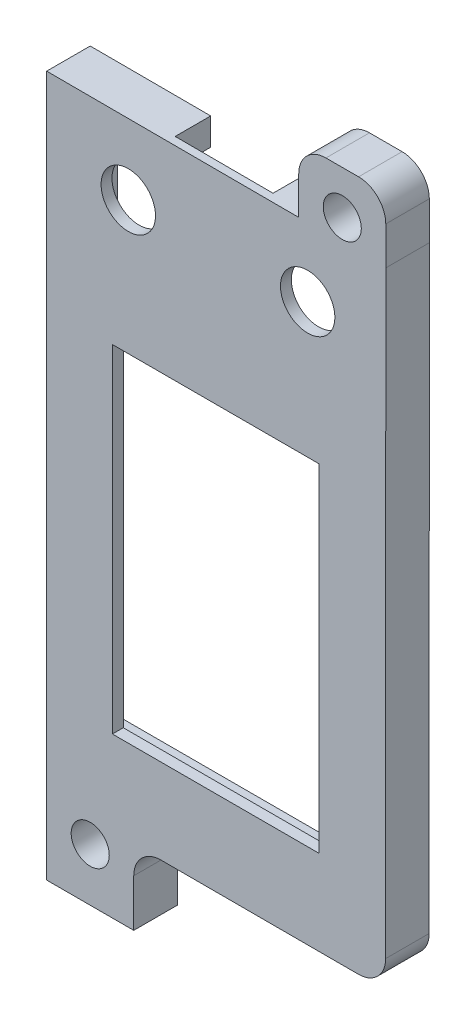
SolidWorks part; units mm, degrees
ref_plane "Front" through (0, 0, 0) normal (0, 0, 1) x (1, 0, 0)
ref_plane "Top" through (0, 0, 0) normal (0, 1, 0) x (1, 0, 0)
ref_plane "Side" through (0, 0, 0) normal (1, 0, 0) x (0, 0, -1)
ref_axis "X_Axis" through (-20.1896, 0, 0) along (1, 0, 0)
ref_axis "Y_Axis" through (0, -14.8261, 0) along (0, 1, 0)
ref_axis "Z_Axis" through (0, 0, -19.842) along (0, 0, 1)
sketch "Sketch1" plane through (0, 0, 0) normal (0, 0, 1) x (1, 0, 0)
  line L0 (-12.1762, 17.3557) -> (13.9737, 17.3297) construction
  line L1 (13.9737, 17.3297) -> (13.9859, 69.814) construction
  line L2 (13.9859, 69.814) -> (-12.1762, 69.8802) construction
  line L3 (-12.1762, 69.8802) -> (-12.1762, 17.3557) construction
  line L4 (-12.1762, 17.3557) -> (13.9737, 17.3297)
  line L5 (13.9737, 17.3297) -> (13.9859, 69.814)
  line L6 (13.9859, 69.814) -> (-12.1762, 69.8802)
  line L7 (-12.1762, 69.8802) -> (-12.1762, 17.3557)
  line L8 (-4.1737, 14.8478) -> (13.9712, 14.8297)
  line L9 (16.4737, 17.3291) -> (16.4865, 72.3076)
  line L10 (-14.6762, 8) -> (-6.6762, 8)
  line L11 (-14.6762, 8) -> (-6.6762, 8)
  line L13 (8.4865, 72.3279) -> (-14.6762, 72.3865)
  line L14 (-14.6762, 72.3865) -> (-14.6762, 8)
  line L15 (-6.6762, 8) -> (-6.6762, 12.3478)
  line L16 (-4.1737, 14.8478) -> (13.9712, 14.8297)
  line L17 (16.4737, 17.3291) -> (16.4865, 72.3076)
  line L21 (8.4865, 72.3279) -> (-14.6762, 72.3865)
  line L22 (-14.6762, 72.3865) -> (-14.6762, 8)
  line L23 (-6.6762, 8) -> (-6.6762, 12.3478)
  line L62 (16.4865, 72.3076) -> (16.4865, 75.8076)
  line L63 (16.4865, 72.3076) -> (16.4865, 75.8076)
  line L64 (13.9865, 78.3076) -> (10.9865, 78.3076)
  line L65 (13.9865, 78.3076) -> (10.9865, 78.3076)
  line L66 (8.4865, 75.8076) -> (8.4865, 72.3279)
  line L67 (8.4865, 75.8076) -> (8.4865, 72.3279)
  circle A1 centre (12.487, 74.3178) radius 1.75
  circle A3 centre (-10.6762, 12.8542) radius 1.75
  arc A5 (13.9712, 14.8297) -> (16.4737, 17.3291) centre (13.9737, 17.3297) ccw
  arc A9 (-4.1737, 14.8478) -> (-6.6762, 12.3478) centre (-4.1762, 12.3478) ccw
  arc A10 (13.9712, 14.8297) -> (16.4737, 17.3291) centre (13.9737, 17.3297) ccw
  arc A14 (-4.1737, 14.8478) -> (-6.6762, 12.3478) centre (-4.1762, 12.3478) ccw
  circle A19 centre (12.487, 74.3178) radius 2 construction
  circle A20 centre (-10.6762, 12.8542) radius 2 construction
  arc A33 (16.4865, 75.8076) -> (13.9865, 78.3076) centre (13.9865, 75.8076) ccw
  arc A34 (16.4865, 75.8076) -> (13.9865, 78.3076) centre (13.9865, 75.8076) ccw
  arc A35 (10.9865, 78.3076) -> (8.4865, 75.8076) centre (10.9865, 75.8076) ccw
  arc A36 (10.9865, 78.3076) -> (8.4865, 75.8076) centre (10.9865, 75.8076) ccw
  dimension "D2" = 3.5
  dimension "D3" = 3.5
  dimension "D1" = 0
extrude "Boss-Extrude1" add sketch "Sketch1" along normal blind 1
sketch "Sketch2" plane through (0, 0, 1) normal (0, 0, 1) x (1, 0, 0)
  line L0 (13.9737, 17.3297) -> (13.9859, 69.814) construction
  line L3 (-12.1762, 21.3302) -> (13.9746, 21.3302)
  line L5 (13.9859, 69.814) -> (-12.1762, 69.8802) construction
  line L6 (-12.1762, 69.8802) -> (-12.1762, 17.3557) construction
  line L7 (13.9746, 21.3302) -> (13.9859, 69.814)
  line L8 (13.9859, 69.814) -> (-12.1762, 69.8802)
  line L9 (-12.1762, 69.8802) -> (-12.1762, 21.3302)
  line L13 (-4.1737, 14.8478) -> (13.9712, 14.8297)
  line L14 (16.4737, 17.3291) -> (16.4865, 72.3076)
  line L18 (8.4865, 72.3279) -> (-14.6762, 72.3865)
  line L19 (-14.6762, 72.3865) -> (-14.6762, 8)
  line L20 (-6.6762, 8) -> (-6.6762, 12.3478)
  line L21 (-4.1737, 14.8478) -> (13.9712, 14.8297)
  line L22 (16.4737, 17.3291) -> (16.4865, 72.3076)
  line L26 (8.4865, 72.3279) -> (-14.6762, 72.3865)
  line L27 (-14.6762, 72.3865) -> (-14.6762, 8)
  line L28 (-6.6762, 8) -> (-6.6762, 12.3478)
  line L32 (16.4865, 72.3076) -> (16.4865, 75.8076)
  line L33 (16.4865, 72.3076) -> (16.4865, 75.8076)
  line L34 (13.9865, 78.3076) -> (10.9865, 78.3076)
  line L35 (13.9865, 78.3076) -> (10.9865, 78.3076)
  line L36 (8.4865, 75.8076) -> (8.4865, 72.3279)
  line L37 (8.4865, 75.8076) -> (8.4865, 72.3279)
  circle A0 centre (12.487, 74.3178) radius 1.75 construction
  circle A1 centre (12.487, 74.3178) radius 1.75
  circle A2 centre (-10.6762, 12.8542) radius 1.75 construction
  circle A3 centre (-10.6762, 12.8542) radius 1.75
  arc A5 (-4.1737, 14.8478) -> (-6.6762, 12.3478) centre (-4.1762, 12.3478) ccw
  arc A6 (13.9712, 14.8297) -> (16.4737, 17.3291) centre (13.9737, 17.3297) ccw
  arc A10 (-4.1737, 14.8478) -> (-6.6762, 12.3478) centre (-4.1762, 12.3478) ccw
  arc A11 (13.9712, 14.8297) -> (16.4737, 17.3291) centre (13.9737, 17.3297) ccw
  arc A16 (16.4865, 75.8076) -> (13.9865, 78.3076) centre (13.9865, 75.8076) ccw
  arc A17 (16.4865, 75.8076) -> (13.9865, 78.3076) centre (13.9865, 75.8076) ccw
  arc A18 (10.9865, 78.3076) -> (8.4865, 75.8076) centre (10.9865, 75.8076) ccw
  arc A19 (10.9865, 78.3076) -> (8.4865, 75.8076) centre (10.9865, 75.8076) ccw
  spline S1 degree 1 poles (-3014.6542, 8) (2993.288, 8) knots -374.997257 -374.997257 375.995518 375.995518 only from (-14.6762, 8) to (-6.6762, 8)
  spline S2 degree 1 poles (-14.6762, 8) (-6.6762, 8) knots 0 0 1 1
  dimension "D1" = 0
extrude "Boss-Extrude2" add sketch "Sketch2" along normal blind 2
sketch "Sketch3" plane through (0, 0, 3) normal (0, 0, 1) x (1, 0, 0)
  line L6 (0.862, 70.6723) -> (0.862, 14.8428) construction
  line L7 (4.032, 70.6723) -> (-2.308, 70.6723) construction
  line L8 (-4.1737, 14.8478) -> (13.9712, 14.8297)
  line L9 (16.4737, 17.3291) -> (16.4865, 72.3076)
  line L10 (16.4865, 72.3076) -> (16.4865, 75.8076)
  line L11 (13.9865, 78.3076) -> (10.9865, 78.3076)
  line L12 (8.4865, 75.8076) -> (8.4865, 72.3279)
  line L13 (8.4865, 72.3279) -> (-14.6762, 72.3865)
  line L14 (-14.6762, 72.3865) -> (-14.6762, 8)
  line L15 (-6.6762, 8) -> (-6.6762, 12.3478)
  line L16 (-4.1737, 14.8478) -> (13.9712, 14.8297)
  line L17 (16.4737, 17.3291) -> (16.4865, 72.3076)
  line L18 (16.4865, 72.3076) -> (16.4865, 75.8076)
  line L19 (13.9865, 78.3076) -> (10.9865, 78.3076)
  line L20 (8.4865, 75.8076) -> (8.4865, 72.3279)
  line L21 (8.4865, 72.3279) -> (-14.6762, 72.3865)
  line L22 (-14.6762, 72.3865) -> (-14.6762, 8)
  line L23 (-6.6762, 8) -> (-6.6762, 12.3478)
  line L25 (-8.5614, 67.8674) -> (-5.7928, 63.8796) construction
  line L26 (-5.7928, 67.8674) -> (-8.5614, 63.8796) construction
  line L27 (7.9232, 68.0198) -> (10.6918, 64.032) construction
  line L28 (10.362, 53.6482) -> (-8.638, 53.6482)
  line L29 (10.362, 53.6482) -> (10.362, 22.6482)
  line L30 (10.362, 22.6482) -> (-8.638, 22.6482)
  line L31 (-8.638, 53.6482) -> (-8.638, 22.6482)
  line L36 (10.6918, 68.0198) -> (10.6918, 64.032) construction
  line L37 (10.6918, 64.032) -> (10.6918, 68.0198) construction
  line L38 (10.6918, 68.0198) -> (7.9232, 64.032) construction
  line L39 (10.362, 53.6482) -> (-8.638, 22.6482) construction
  line L40 (10.362, 22.6482) -> (-8.638, 53.6482) construction
  circle A0 centre (-7.1771, 65.8735) radius 2.5
  circle A1 centre (9.3075, 66.0259) radius 2.5
  circle A2 centre (12.487, 74.3178) radius 1.75 construction
  circle A3 centre (12.487, 74.3178) radius 1.75
  circle A4 centre (-10.6762, 12.8542) radius 1.75 construction
  arc A5 (-4.1737, 14.8478) -> (-6.6762, 12.3478) centre (-4.1762, 12.3478) ccw
  arc A6 (13.9712, 14.8297) -> (16.4737, 17.3291) centre (13.9737, 17.3297) ccw
  arc A7 (16.4865, 75.8076) -> (13.9865, 78.3076) centre (13.9865, 75.8076) ccw
  arc A8 (10.9865, 78.3076) -> (8.4865, 75.8076) centre (10.9865, 75.8076) ccw
  arc A10 (-4.1737, 14.8478) -> (-6.6762, 12.3478) centre (-4.1762, 12.3478) ccw
  arc A11 (13.9712, 14.8297) -> (16.4737, 17.3291) centre (13.9737, 17.3297) ccw
  arc A12 (16.4865, 75.8076) -> (13.9865, 78.3076) centre (13.9865, 75.8076) ccw
  arc A13 (10.9865, 78.3076) -> (8.4865, 75.8076) centre (10.9865, 75.8076) ccw
  circle A15 centre (-10.6762, 12.8542) radius 1.75
  spline S1 degree 1 poles (-3014.6542, 8) (2993.288, 8) knots -374.997257 -374.997257 375.995518 375.995518 only from (-14.6762, 8) to (-6.6762, 8)
  spline S2 degree 1 poles (-14.6762, 8) (-6.6762, 8) knots 0 0 1 1
  point P29 (0.862, 38.1482)
  dimension "D3" = 5
  dimension "D2" = 31
  dimension "D4" = 19
  dimension "D5" = 4
  dimension "D1" = 0
extrude "Boss-Extrude3" add sketch "Sketch3" along normal blind 1
sketch "Sketch5" plane through (-14.6762, 0, 0) normal (-1, 0, 0) x (0, 0, 1)
  line L0 (-1.0102, 47.7252) -> (-1.0102, 67.4902) construction
  line L1 (-1.0102, 55.1394) -> (2.5898, 55.1394)
  line L2 (-1.0102, 55.1394) -> (-1.0102, 59.7394)
  line L3 (-1.0102, 59.7394) -> (2.5898, 59.7394)
  line L4 (2.5898, 55.1394) -> (2.5898, 59.7394)
  line L5 (2.0418, 57.428) -> (-1.0102, 57.4394) construction
  line L6 (2.0418, 55.142) -> (2.0418, 59.714) construction
  dimension "D1" = 3.6
  dimension "D2" = 4.6
extrude "Cut-Extrude1" cut sketch "Sketch5" against normal blind 21
sketch "Sketch6" plane through (0.1831, 72.3489, 0) normal (0.0025, 1, 0) x (1, -0.0025, 0)
  line L1 (-3.7868, -3.2648) -> (5.2084, -3.2648)
  line L2 (-3.7868, -3.2648) -> (-3.7868, 0)
  line L3 (-3.7868, 0) -> (5.2084, 0)
  line L4 (5.2084, -3.2648) -> (5.2084, 0)
extrude "Cut-Extrude2" cut sketch "Sketch6" against normal blind 21
